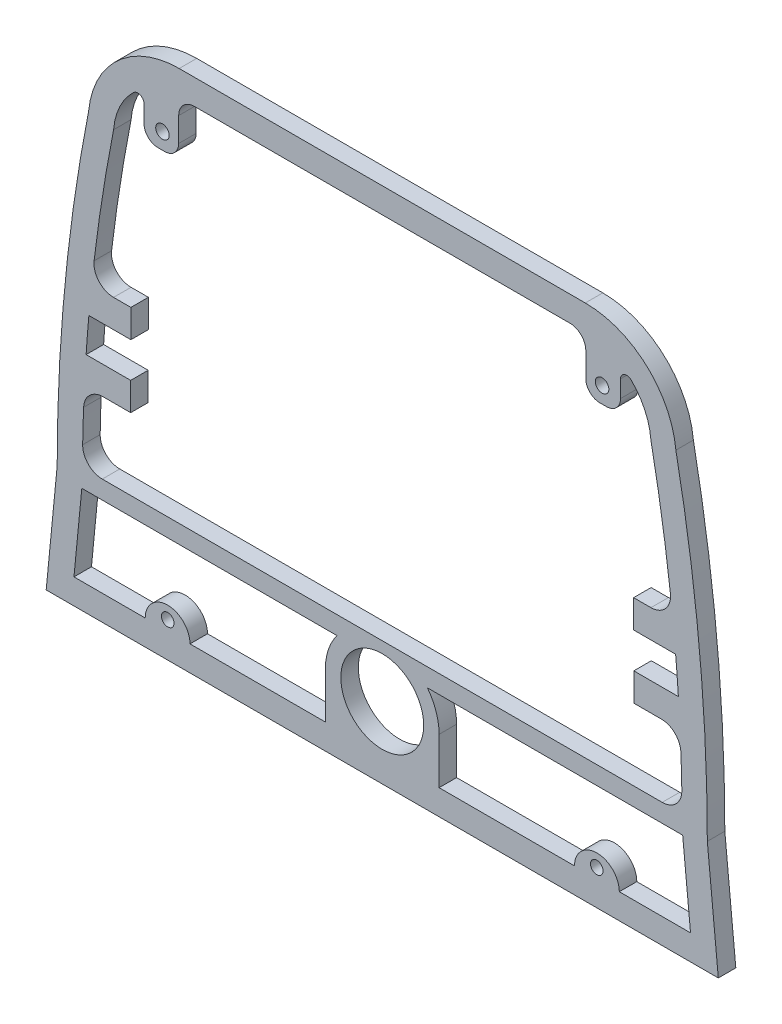
SolidWorks part; units mm, degrees
material "Delrin 2700 NC010, Low Viscosity Acetal Copolymer (SS)"
ref_plane "Front Plane" through (0, 0, 0) normal (0, 0, 1) x (1, 0, 0)
ref_plane "Top Plane" through (0, 0, 0) normal (0, 1, 0) x (1, 0, 0)
ref_plane "Right Plane" through (0, 0, 0) normal (1, 0, 0) x (0, 0, -1)
sketch "Sketch1" plane through (0, 0, 0) normal (0, 0, 1) x (1, 0, 0)
  line L0 (29.4835, -11.9888) -> (30.48, -22.225)
  line L1 (18.415, 24.765) -> (-18.415, 24.765)
  line L2 (-30.48, -22.225) -> (-26.6312, 17.3099) construction
  line L3 (-29.4835, -11.9888) -> (-29.4835, 14.6458) construction
  line L4 (-29.4835, -11.9888) -> (-30.48, -22.225)
  line L5 (18.415, 22.479) -> (-18.415, 22.479)
  line L6 (27.1974, -12.0994) -> (27.9606, -19.939)
  line L7 (-27.9606, -19.939) -> (27.9606, -19.939)
  line L8 (-30.48, -22.225) -> (30.48, -22.225)
  line L9 (-27.1974, -12.0994) -> (-27.9606, -19.939)
  line L10 (-18.4627, 22.479) -> (-18.4627, 18.8517)
  line L11 (-19.7327, 17.5817) -> (-20.3405, 17.5817)
  line L12 (-21.6105, 18.8517) -> (-21.6105, 21.5516)
  line L13 (18.4627, 22.479) -> (18.4627, 18.8517)
  line L14 (19.7327, 17.5817) -> (20.3405, 17.5817)
  line L15 (21.6105, 18.8517) -> (21.6105, 21.5516)
  line L16 (-22.7988, 1.27) -> (-22.7988, 3.81)
  line L17 (26.6088, 1.27) -> (22.7988, 1.27)
  line L18 (0, 18.415) -> (0, -18.415) construction
  line L19 (-1007.9925, 0) -> (48992.0075, 0) construction
  line L20 (22.8175, -4.4704) -> (22.8175, -1.9304)
  line L21 (26.361, 3.81) -> (22.7988, 3.81)
  line L22 (22.7988, 1.27) -> (22.7988, 3.81)
  line L23 (-26.361, 3.81) -> (-22.7988, 3.81)
  line L24 (-26.8081, -2.2098) -> (26.7859, -2.2098) construction
  line L25 (-26.8081, -2.2098) -> (-26.8081, -11.9888) construction
  line L26 (-26.8081, -11.9888) -> (26.8081, -11.9888) construction
  line L27 (26.7859, -2.2098) -> (26.7859, -11.9888) construction
  line L28 (-27.0085, -4.4704) -> (-22.8175, -4.4704)
  line L29 (-26.6088, 1.27) -> (-22.7988, 1.27)
  line L30 (26.859, -1.9304) -> (22.8175, -1.9304)
  line L31 (-26.859, -1.9304) -> (-22.8175, -1.9304)
  line L32 (-22.8175, -4.4704) -> (-22.8175, -1.9304)
  line L33 (27.0085, -4.4704) -> (22.8175, -4.4704)
  line L34 (-27.194, -10.9728) -> (27.194, -10.9728)
  line L35 (-5.1562, -15.748) -> (-5.1562, -19.939)
  line L36 (-27.2485, -12.6238) -> (-4.1019, -12.6238)
  line L37 (4.1019, -12.6238) -> (27.2485, -12.6238)
  line L38 (-27.194, -12.6238) -> (27.194, -12.6238) construction
  line L39 (5.1562, -15.748) -> (5.1562, -19.939)
  arc A0 (18.415, 24.765) -> (26.6312, 17.3099) centre (18.415, 16.51) cw
  arc A1 (-18.415, 24.765) -> (-26.6312, 17.3099) centre (-18.415, 16.51) ccw
  arc A2 (29.4835, -11.9888) -> (26.6312, 17.3099) centre (-122.4189, -11.9888) ccw
  circle A3 centre (0, -15.748) radius 3.7592
  circle A4 centre (19.4575, -19.05) radius 0.5715
  arc A5 (-29.4835, -11.9888) -> (-26.6312, 17.3099) centre (122.4189, -11.9888) cw
  arc A6 (-27.1974, -12.0994) -> (-24.365, 16.9863) centre (122.4189, -11.9888) cw
  arc A7 (-20.3405, 17.5817) -> (-21.6105, 18.8517) centre (-20.3405, 18.8517) cw
  arc A8 (-4.1019, -12.6238) -> (-5.1562, -15.748) centre (0, -15.748) ccw
  circle A9 centre (-19.939, 19.05) radius 0.6096
  circle A10 centre (19.939, 19.05) radius 0.6096
  arc A11 (-21.5006, -19.939) -> (-17.4366, -19.939) centre (-19.4686, -19.939) cw
  circle A12 centre (-19.4575, -19.05) radius 0.5715
  arc A13 (21.5006, -19.939) -> (17.4366, -19.939) centre (19.4686, -19.939) ccw
  arc A14 (-18.4627, 18.8517) -> (-19.7327, 17.5817) centre (-19.7327, 18.8517) cw
  arc A15 (-17.0301, 22.479) -> (-18.4627, 21.0463) centre (-17.0301, 21.0463) ccw
  arc A16 (-21.6105, 20.4037) -> (-22.5586, 20.8065) centre (-22.1701, 20.4037) ccw
  arc A17 (17.0301, 22.479) -> (18.4627, 21.0463) centre (17.0301, 21.0463) cw
  arc A18 (-18.415, 22.479) -> (-24.365, 16.9863) centre (-18.415, 16.51) ccw
  arc A19 (18.415, 22.479) -> (24.365, 16.9863) centre (18.415, 16.51) cw
  arc A20 (27.1974, -12.0994) -> (24.365, 16.9863) centre (-122.4189, -11.9888) ccw
  arc A21 (18.4627, 18.8517) -> (19.7327, 17.5817) centre (19.7327, 18.8517) ccw
  arc A22 (20.3405, 17.5817) -> (21.6105, 18.8517) centre (20.3405, 18.8517) ccw
  arc A23 (21.6105, 20.4037) -> (22.5586, 20.8065) centre (22.1701, 20.4037) cw
  circle A24 centre (0, -15.748) radius 5.1562 construction
  arc A25 (4.1019, -12.6238) -> (5.1562, -15.748) centre (0, -15.748) cw
  point P0 (0, 0)
  point P1 (0, 24.765)
  point P26 (0, -22.225)
  point P31 (0, -11.9888)
  point P104 (-3.7592, -15.748)
  dimension "D4" = 2.286
  dimension "D6" = 8.255
  dimension "D7" = 19.4575
  dimension "D8" = 46.99
  dimension "D9" = 15.748
  dimension "D5" = 1.2192
  dimension "D17" = 1.143
  dimension "D3" = 7.5184
  dimension "D18" = 2.032
  dimension "D19" = 1.27
  dimension "D20" = 1.27
  dimension "D2" = 36.83
  dimension "D10" = 19.05
  dimension "D11" = 19.05
  dimension "D12" = 60.96
  dimension "D13" = 19.939
  dimension "D14" = 22.225
  dimension "D15" = 53.594
  dimension "D16" = 9.779
  dimension "D21" = 1.27
  dimension "D22" = 2.54
  dimension "D23" = 3.81
  dimension "D24" = 2.54
  dimension "D25" = 3.2004
  dimension "D26" = 4.191
  dimension "D27" = 1.016
  dimension "D28" = 1.651
  dimension "D29" = 1.397
extrude "Boss-Extrude1" add sketch "Sketch1" along normal blind 1.5875 contours L8 A12 A4 L0 A2 A0 L1 A1 A5 L4 A20 L6 L7 L9 A6 A18 L5 A19 | L5 A18 A9 | A19 L5 A10 | A11 L7 A12 | L7 A13 A4 | A15 L5 L10 | L12 A18 A16 | L5 A17 L13 | L15 A23 A19 | L17 A20 L21 L22 | A6 L29 L16 L23 | A6 L28 L32 L31 | L33 A20 L30 L20 | A25 L37 L6 A20 L34 A6 L9 L36 A8 L35 L7 L39 A3 region at (29.2157, -17.1815, 0) region at (18.1427, 22.159, 0) region at (19.986, 20.0753, 0) region at (-18.1427, 22.159, 0) region at (21.8567, 21.091, 0) region at (-19.986, 20.0753, 0) region at (-21.8567, 21.091, 0) region at (24.6444, 2.5258, 0) region at (24.8776, -3.2081, 0) region at (-24.6444, 2.5258, 0) region at (26.6445, -11.5378, 0) region at (-24.8776, -3.2081, 0) region at (19.4686, -19.8936, 0) region at (-19.4686, -17.9524, 0)
ref_axis "Axis1" through (0, -15.748, 0) along (0, 0, 1)
fillet "Fillet1" radius 1.778 6 edges at (26.361, 3.81, 0.7937) (27.194, -10.9728, 0.7937) (27.0085, -4.4704, 0.7937) (-27.0085, -4.4704, 0.7937) (-27.194, -10.9728, 0.7937) (-26.361, 3.81, 0.7937)
